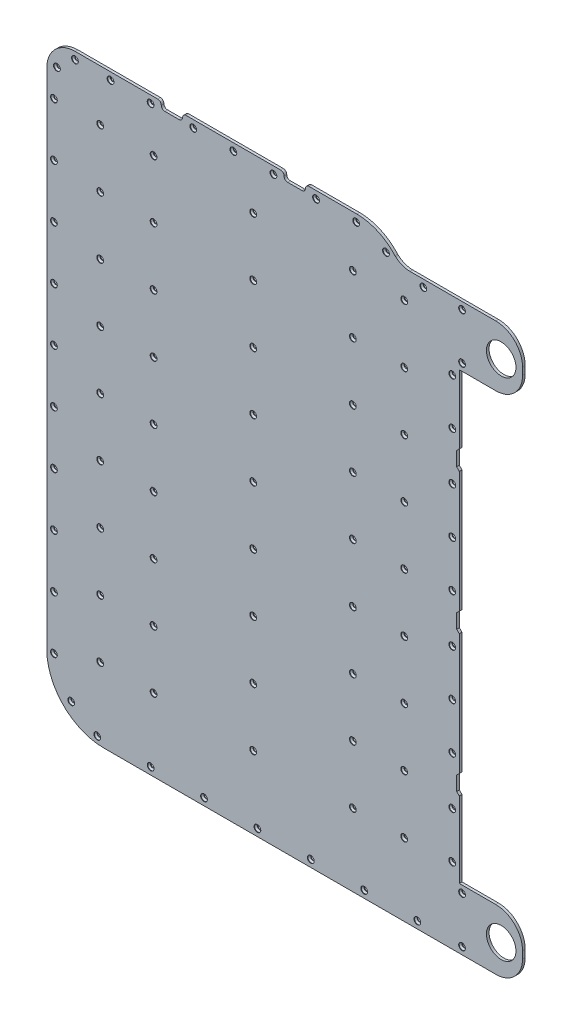
SolidWorks part; units mm, degrees
ref_plane "Front Plane" through (0, 0, 0) normal (0, 0, 1) x (1, 0, 0)
ref_plane "Top Plane" through (0, 0, 0) normal (0, 1, 0) x (1, 0, 0)
ref_plane "Right Plane" through (0, 0, 0) normal (1, 0, 0) x (0, 0, -1)
ref_plane "Plane1" through (0, 0, 1.5) normal (0, 0, 1) x (1, 0, 0)
sketch "Sketch1" plane through (0, 0, 1.5) normal (0, 0, 1) x (1, 0, 0)
  line L0 (267.3541, 331) -> (0, 331)
  line L1 (0, 331) -> (0, 0)
  line L2 (0, 0) -> (267.3541, 0)
  line L3 (267.3541, 0) -> (267.3541, 331)
extrude "Boss-Extrude1" add sketch "Sketch1" against normal blind 1.5
sketch "Sketch2" plane through (0, 0, 0) normal (0, 0, -1) x (-1, 0, 0)
  line L0 (-267.3541, 284) -> (-267.3541, 33.9844)
  line L1 (-267.3541, 33.9844) -> (-231.8079, 33.9844)
  line L2 (-231.8079, 33.9844) -> (-231.8148, 76.5759)
  line L3 (-231.8148, 76.5759) -> (-230.3541, 78)
  line L4 (-230.3541, 78) -> (-230.3541, 86)
  line L5 (-230.3541, 86) -> (-231.8165, 87.5)
  line L6 (-231.8165, 87.5) -> (-231.8274, 155.5)
  line L7 (-231.8274, 155.5) -> (-230.3541, 157)
  line L8 (-230.3541, 157) -> (-230.3541, 165)
  line L9 (-230.3541, 165) -> (-231.8292, 166.5)
  line L10 (-231.8292, 166.5) -> (-231.8401, 234.5)
  line L11 (-231.8401, 234.5) -> (-230.3541, 236)
  line L12 (-230.3541, 236) -> (-230.3541, 244)
  line L13 (-230.3541, 244) -> (-231.8419, 245.5)
  line L14 (-231.8419, 245.5) -> (-231.8481, 284)
  line L15 (-231.8481, 284) -> (-267.3541, 284)
extrude "Cut-Extrude1" cut sketch "Sketch2" against normal through all
sketch "Sketch3" plane through (0, 0, 0) normal (0, 0, -1) x (-1, 0, 0)
  line L0 (-174.2254, 331) -> (-267.3541, 331)
  line L1 (-267.3541, 331) -> (-267.3541, 318)
  line L2 (-267.3541, 318) -> (-199.4999, 318)
  line L3 (-199.4999, 318) -> (-195.6927, 321.4126)
  arc A0 (-195.6927, 321.4126) -> (-174.2254, 331) centre (-174.1533, 302.0108) cw
extrude "Cut-Extrude2" cut sketch "Sketch3" against normal through all
sketch "Sketch4" plane through (0, 0, 0) normal (0, 0, -1) x (-1, 0, 0)
  line L0 (-131.3541, 331) -> (-147.3541, 331)
  line L1 (-143.3541, 327) -> (-135.3541, 327)
  arc A0 (-147.3541, 331) -> (-145.3541, 329) centre (-147.3541, 329) cw
  arc A1 (-145.3541, 329) -> (-143.3541, 327) centre (-143.3541, 329) ccw
  arc A2 (-135.3541, 327) -> (-133.3541, 329) centre (-135.3541, 329) ccw
  arc A3 (-133.3541, 329) -> (-131.3541, 331) centre (-131.3541, 329) cw
extrude "Cut-Extrude3" cut sketch "Sketch4" against normal through all
sketch "Sketch5" plane through (0, 0, 0) normal (0, 0, -1) x (-1, 0, 0)
  line L0 (-62.3259, 331) -> (-78.3259, 331)
  line L1 (-74.3259, 327) -> (-66.3259, 327)
  arc A0 (-78.3259, 331) -> (-76.3259, 329) centre (-78.3259, 329) cw
  arc A1 (-76.3259, 329) -> (-74.3259, 327) centre (-74.3259, 329) ccw
  arc A2 (-66.3259, 327) -> (-64.3259, 329) centre (-66.3259, 329) ccw
  arc A3 (-64.3259, 329) -> (-62.3259, 331) centre (-62.3259, 329) cw
extrude "Cut-Extrude4" cut sketch "Sketch5" against normal through all
hole_wizard "M14 Clearance Hole1" positions "Sketch7" profile "Sketch6" hole size "M14" standard "ANSI Metric"
sketch "Sketch7" plane through (0, 0, 1.5) normal (0, 0, 1) x (1, 0, 0)
  point P0 (255.3541, 16.9922)
  point P1 (255.3541, 301.0078)
sketch "Sketch6" plane through (255.3541, 16.9922, 1.5) normal (1, 0, 0) x (0, -1, 0)
  line L0 (0, 0) -> (0, 1.5)
  line L1 (0, 1.5) -> (8.075, 1.5)
  line L2 (8.075, 1.5) -> (8.075, 0)
  line L5 (8.075, 0) -> (0, 0)
  line L11 (0, -6.35) -> (0, 107.95) construction
  dimension "Thru Hole Dia." = 16.15
  dimension "Thru Hole Depth" = 1.5
hole_wizard "CSK for M2 Flat Head Machine Screw1" positions "Sketch9" profile "Sketch8" countersink size "M2" standard "ANSI Metric"
sketch "Sketch9" plane through (0, 0, 1.5) normal (0, 0, 1) x (1, 0, 0)
  point P0 (178.3541, 4)
  point P1 (116, 106.1)
  point P2 (60, 236.9)
  point P3 (30, 138.8)
  point P4 (118.3541, 4)
  point P5 (28.3541, 4)
  point P6 (227.8315, 95.5)
  point P7 (30, 269.6)
  point P8 (116, 236.9)
  point P9 (227.8399, 147.5)
  point P10 (172, 171.5)
  point P11 (58.3541, 4)
  point P12 (30, 171.5)
  point P13 (200.8329, 73.4)
  point P14 (4, 242)
  point P15 (60, 40.7)
  point P16 (4, 152)
  point P17 (13.7, 13.5)
  point P18 (15.8259, 326.8572)
  point P19 (227.8442, 174.5)
  point P20 (200.8592, 236.9)
  point P21 (4, 302)
  point P22 (151.3173, 326.8572)
  point P23 (173.8541, 326.8572)
  point P24 (200.8644, 269.6)
  point P25 (233.3541, 314)
  point P26 (190.6047, 320.573)
  point P27 (227.8526, 226.5)
  point P28 (30, 106.1)
  point P29 (227.8611, 279.5)
  point P30 (172, 236.9)
  point P31 (227.823, 42.5)
  point P32 (116, 269.6)
  point P33 (35.8259, 326.8572)
  point P34 (172, 302.3)
  point P35 (116, 302.3)
  point P36 (116, 171.5)
  point P37 (116, 138.8)
  point P38 (4, 32)
  point P39 (5.7053, 318.108)
  point P40 (172, 204.2)
  point P41 (200.8277, 40.7)
  point P42 (172, 73.4)
  point P43 (60, 106.1)
  point P44 (4, 272)
  point P45 (127.3541, 326.8572)
  point P46 (60, 138.8)
  point P47 (4, 212)
  point P48 (233.3541, 29.9844)
  point P49 (227.8272, 68.5)
  point P50 (60, 73.4)
  point P51 (200.8697, 302.3)
  point P52 (200.8434, 138.8)
  point P53 (82.3541, 326.8572)
  point P54 (104.8541, 326.8572)
  point P55 (60, 302.3)
  point P56 (58.3259, 326.8572)
  point P57 (116, 204.2)
  point P58 (88.3541, 4)
  point P59 (30, 40.7)
  point P60 (116, 73.4)
  point P61 (233.3541, 288)
  point P62 (211.6057, 314)
  point P63 (227.8569, 253.5)
  point P64 (200.8539, 204.2)
  point P65 (227.8484, 200.5)
  point P66 (200.8487, 171.5)
  point P67 (60, 269.6)
  point P68 (172, 269.6)
  point P69 (60, 171.5)
  point P70 (4, 122)
  point P71 (148.3541, 4)
  point P72 (4, 62)
  point P73 (116, 40.7)
  point P74 (4, 92)
  point P75 (30, 204.2)
  point P76 (30, 236.9)
  point P77 (172, 106.1)
  point P78 (227.8357, 121.5)
  point P79 (200.8382, 106.1)
  point P80 (4, 182)
  point P81 (60, 204.2)
  point P82 (172, 40.7)
  point P83 (208.2291, 4)
  point P84 (172, 138.8)
  point P85 (30, 73.4)
  point P86 (233.3541, 4)
  point P87 (30, 302.3)
sketch "Sketch8" plane through (178.3541, 4, 1.5) normal (1, 0, 0) x (0, -1, 0)
  line L0 (0, 0) -> (0, 1.5)
  line L1 (0, 1.5) -> (1.1, 1.5)
  line L2 (1.1, 1.5) -> (1.1, 1.1)
  line L3 (1.1, 1.1) -> (1.9, 0.3)
  line L4 (1.9, 0.3) -> (1.9, 0)
  line L6 (1.9, 0) -> (0, 0)
  line L7 (-1.1, 1.1) -> (-1.9, 0.3) construction
  line L11 (0, -6.35) -> (0, 107.95) construction
  dimension "Thru Hole Dia." = 2.2
  dimension "Thru Hole Depth" = 1.5
  dimension "C'Sink Dia." = 3.8
  dimension "C'Sink Angle" = 90
  dimension "Head Clearance" = 0.3
fillet "Fillet1" radius 12 1 edges at (199.4999, 318, 0.75) tangent propagation no
fillet "Fillet2" radius 16 1 edges at (0, 331, 0.75) tangent propagation no
fillet "Fillet3" radius 32 1 edges at (0, 0, 0.75) tangent propagation no
fillet "Fillet4" radius 15 4 edges at (267.3541, 318, 0.75) (267.3541, 284, 0.75) (267.3541, 33.9844, 0.75) (267.3541, 0, 0.75)
sketch "Sketch10" plane through (0, 0, 1.5) normal (0, 0, 1) x (1, 0, 0)
  circle A0 centre (255.3541, 16.9922) radius 8.3
  circle A1 centre (255.3541, 301.0078) radius 8.3
  dimension "D1" = 16.6
  dimension "D2" = 16.6
extrude "Cut-Extrude5" cut sketch "Sketch10" against normal blind 10
